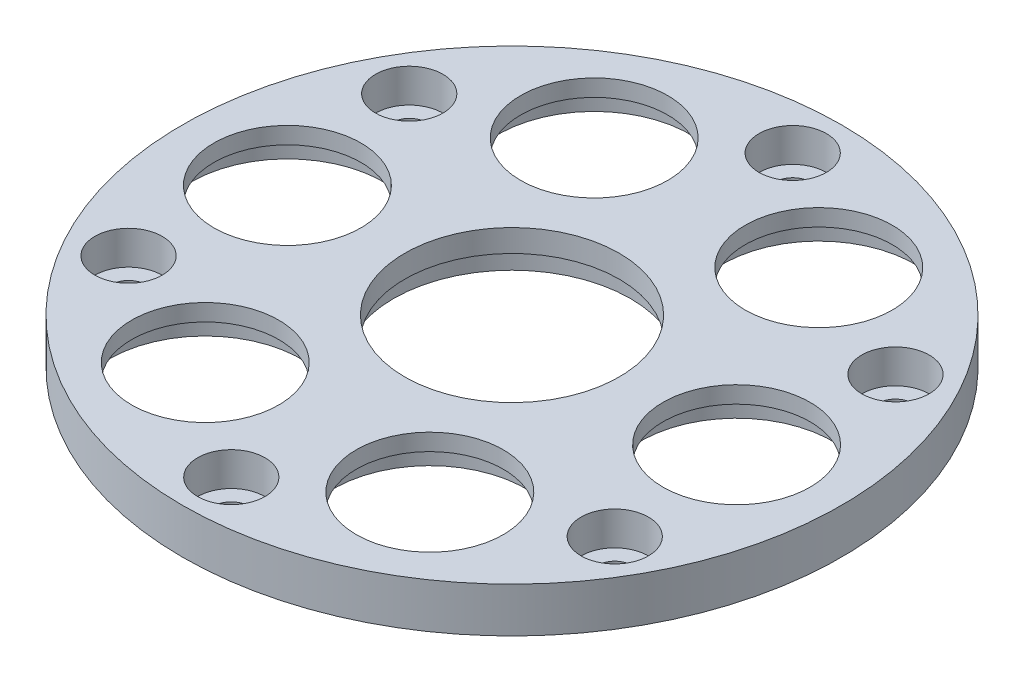
SolidWorks part; units mm, degrees
ref_plane "Front Plane" through (0, 0, 0) normal (0, 0, 1) x (1, 0, 0)
ref_plane "Top Plane" through (0, 0, 0) normal (0, 1, 0) x (1, 0, 0)
ref_plane "Right Plane" through (0, 0, 0) normal (1, 0, 0) x (0, 0, -1)
sketch "Sketch1" plane through (0, 0, 0) normal (0, 1, 0) x (1, 0, 0)
  line L0 (0, 0) -> (-20, 0) construction
  line L1 (-28.55, 0) -> (-29.35, 0) construction
  line L2 (0, 0) -> (0, 25) construction
  circle A0 centre (0, 0) radius 10.55
  circle A1 centre (-20, 0) radius 8.55
  circle A2 centre (0, 0) radius 9.55
  circle A3 centre (-20, 0) radius 6.55
  circle A4 centre (0, 0) radius 29.35
  circle A5 centre (-10, 17.3205) radius 8.55
  circle A6 centre (-10, 17.3205) radius 6.55
  circle A7 centre (10, 17.3205) radius 8.55
  circle A8 centre (10, 17.3205) radius 6.55
  circle A9 centre (20, 0) radius 8.55
  circle A10 centre (20, 0) radius 6.55
  circle A11 centre (10, -17.3205) radius 8.55
  circle A12 centre (10, -17.3205) radius 6.55
  circle A13 centre (-10, -17.3205) radius 8.55
  circle A14 centre (-10, -17.3205) radius 6.55
  circle A15 centre (0, 25) radius 1.55
  circle A16 centre (0, 25) radius 3
  circle A17 centre (21.6506, 12.5) radius 3
  circle A18 centre (21.6506, 12.5) radius 1.55
  circle A19 centre (21.6506, -12.5) radius 3
  circle A20 centre (21.6506, -12.5) radius 1.55
  circle A21 centre (0, -25) radius 3
  circle A22 centre (0, -25) radius 1.55
  circle A23 centre (-21.6506, -12.5) radius 3
  circle A24 centre (-21.6506, -12.5) radius 1.55
  circle A25 centre (-21.6506, 12.5) radius 3
  circle A26 centre (-21.6506, 12.5) radius 1.55
  dimension "D1" = 21.1
  dimension "D2" = 17.1
  dimension "D8" = 3.1
  dimension "D9" = 6
  dimension "D3" = 20
  dimension "D4" = 0.8
  dimension "D5" = 2
  dimension "D6" = 1
  dimension "D10" = 25
  dimension "D7" = 6
extrude "Boss-Extrude1" add sketch "Sketch1" against normal blind 4 contours A4
extrude "Cut-Extrude1" cut sketch "Sketch1<4>" against normal through all contours A3 | A14 | A12 | A10 | A8 | A6 | A24 | A22 | A20 | A18 | A15 | A26 | A2 region at (0, 0, 0) region at (-20, 0, 0) region at (-10, 0, -17.3205) region at (10, 0, -17.3205) region at (20, 0, 0) region at (10, 0, 17.3205) region at (-10, 0, 17.3205) region at (0, 0, -25) region at (21.6506, 0, -12.5) region at (21.6506, 0, 12.5) region at (0, 0, 25) region at (-21.6506, 0, 12.5) region at (-21.6506, 0, -12.5)
sketch "Sketch1<4>" plane through (0, 0, 0) normal (0, 1, 0) x (1, 0, 0) same geometry as "Sketch1"
extrude "Cut-Extrude2" cut sketch "Sketch1<5>" against normal through all from offset 1.5 contours A1 A3 | A5 A6 | A7 A8 | A9 A10 | A11 A12 | A13 A14 region at (-28.3082, 0, 0) region at (-18.3082, 0, -17.3205) region at (1.6918, 0, -17.3205) region at (11.6918, 0, 0) region at (1.6918, 0, 17.3205) region at (-18.3082, 0, 17.3205) offset against normal yes
sketch "Sketch1<5>" plane through (0, 0, 0) normal (0, 1, 0) x (1, 0, 0) same geometry as "Sketch1"
extrude "Cut-Extrude3" cut sketch "Sketch1<6>" against normal through all from offset 2 contours A0 A2 region at (-10.2516, 0, 0) offset against normal yes
sketch "Sketch1<6>" plane through (0, 0, 0) normal (0, 1, 0) x (1, 0, 0) same geometry as "Sketch1"
extrude "Cut-Extrude4" cut sketch "Sketch1<7>" against normal blind 3 contours A25 A26 | A16 A15 | A17 A18 | A19 A20 | A21 A22 | A23 A24 region at (-2.9151, 0, -25) region at (18.7355, 0, -12.5) region at (18.7355, 0, 12.5) region at (-2.9151, 0, 25) region at (-24.5658, 0, 12.5) region at (-24.5658, 0, -12.5)
sketch "Sketch1<7>" plane through (0, 0, 0) normal (0, 1, 0) x (1, 0, 0) same geometry as "Sketch1"
equation "\"Ratio\"= 15"
equation "\"Hull Diameter\"= 92"
equation "\"Fixed Ring Diameter\"= 76"
equation "\"Fixed Pin Diameter\"= 6"
equation "\"Output Ring Diameter\"= 40"
equation "\"Output Pin Diameter\"= 6"
equation "\"Disk Bearing Inner Diameter\"= 9"
equation "\"Disk Bearing Outer Diameter\"= 17"
equation "\"Disk Bearing Height\"= 5"
equation "\"Shaft Bearing Inner Diameter\"= 15"
equation "\"Shaft Bearing Outer Diameter\"= 21"
equation "\"Shaft Bearing Height\"= 4"
equation "\"Eccentricity\"= 1.5"
equation "\"Disk Height\"= 8"
equation "\"Disk Spacing\"= 5"
equation "\"Hull Height\"= 40"
equation "\"Shaft End Bearing Inner Diameter\"= 12"
equation "\"Shaft End Bearing Outer Diameter\"= 18"
equation "\"Shaft End Bearing Height\"= 4"
equation "\"Output Bearing Inner Diameter\"= 55"
equation "\"Output Bearing Outer Diameter\"= 72"
equation "\"Outer Bearing Height\"= 9"
equation "\"D1@Sketch1\"=\"Shaft Bearing Outer Diameter\"+0.1"
equation "\"D2@Sketch1\"=\"Disk Bearing Outer Diameter\"+0.1"
equation "\"D3@Sketch1\"=\"Output Ring Diameter\"/2"
